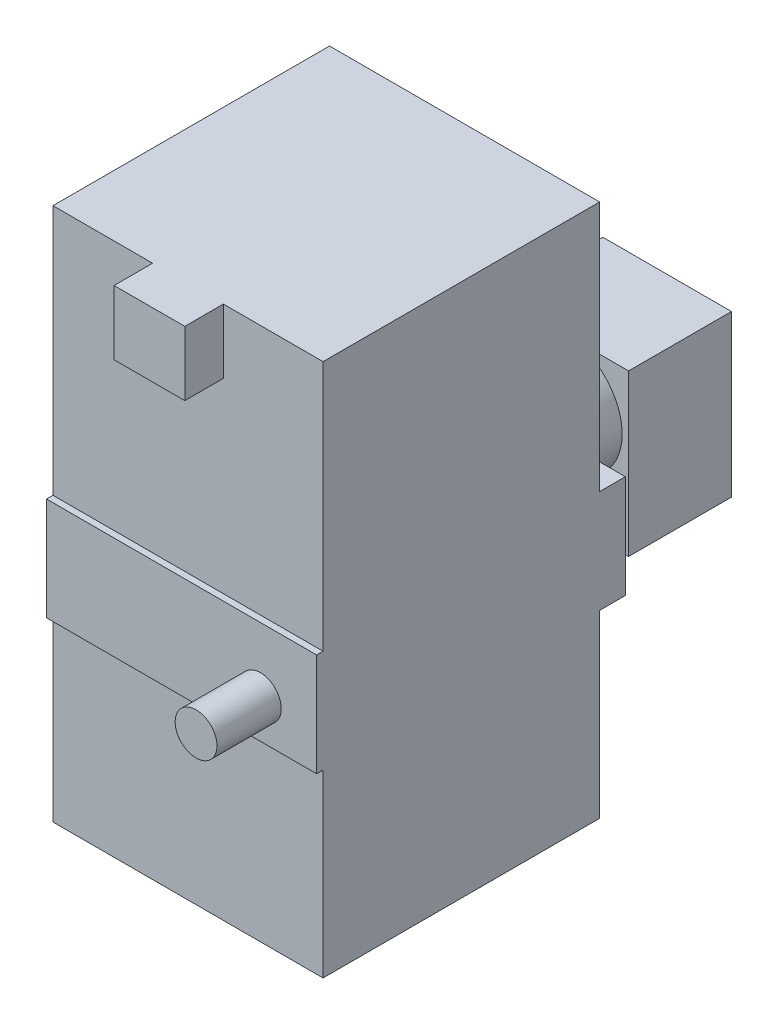
SolidWorks part; units mm, degrees
ref_plane "Alzado" through (0, 0, 0) normal (0, 0, 1) x (1, 0, 0)
ref_plane "Planta" through (0, 0, 0) normal (0, 1, 0) x (1, 0, 0)
ref_plane "Vista lateral" through (0, 0, 0) normal (1, 0, 0) x (0, 0, -1)
sketch "Croquis1" plane through (0, 0, 0) normal (1, 0, 0) x (0, 0, -1)
  line L0 (21.5, 2.5) -> (25.5, 2.5)
  line L1 (21.5, -41.5) -> (-21.5, -41.5)
  line L2 (21.5, -41.5) -> (21.5, -13.5)
  line L3 (21.5, 41.5) -> (-21.5, 41.5)
  line L4 (-21.5, -41.5) -> (-21.5, -13.5)
  line L5 (21.5, -41.5) -> (-21.5, 41.5) construction
  line L6 (21.5, 41.5) -> (-21.5, -41.5) construction
  line L7 (-22.5, -13.5) -> (-21.5, -13.5)
  line L8 (-22.5, -13.5) -> (-22.5, 2.5)
  line L9 (-22.5, 2.5) -> (-21.5, 2.5)
  line L10 (25.5, -13.5) -> (25.5, 2.5)
  line L11 (21.5, 2.5) -> (21.5, 41.5)
  line L12 (21.5, -13.5) -> (25.5, -13.5)
  line L13 (-21.5, 2.5) -> (-21.5, 41.5)
  point P0 (0, 0)
  dimension "D1" = 43
  dimension "D2" = 83
  dimension "D3" = 48
  dimension "D4" = 4
  dimension "D5" = 16
  dimension "D6" = 39
extrude "Saliente-Extruir1" add sketch "Croquis1" along normal blind 42
sketch "Croquis2" plane through (0, 0, 21.5) normal (0, 0, 1) x (1, 0, 0)
  line L0 (42, 41.5) -> (0, 41.5) construction
  line L1 (15.5, 41.5) -> (26.5, 41.5)
  line L2 (15.5, 41.5) -> (15.5, 31.5)
  line L3 (15.5, 31.5) -> (26.5, 31.5)
  line L4 (26.5, 41.5) -> (26.5, 31.5)
  line L5 (15.5, 41.5) -> (0, 41.5) construction
  line L6 (26.5, 41.5) -> (42, 41.5) construction
  dimension "D1" = 10
  dimension "D2" = 11
extrude "Saliente-Extruir2" add sketch "Croquis2" along normal blind 6
sketch "Croquis3" plane through (0, 0, 22.5) normal (0, 0, 1) x (1, 0, 0)
  line L0 (42, 2.5) -> (0, 2.5) construction
  line L1 (42, 2.5) -> (42, -13.5) construction
  circle A0 centre (33.25, -7.5) radius 3.25
  dimension "D1" = 6.5
  dimension "D2" = 10
  dimension "D3" = 8.75
extrude "Saliente-Extruir3" add sketch "Croquis3" along normal blind 10
sketch "Croquis4" plane through (0, 0, -25.5) normal (0, 0, -1) x (-1, 0, 0)
  line L1 (-42, 2.5) -> (0, 2.5) construction
  line L3 (0, -13.5) -> (0, 2.5) construction
  circle A0 centre (-16, -8.5) radius 9
  dimension "D2" = 18
  dimension "D3" = 16
  dimension "D1" = 11
extrude "Saliente-Extruir4" add sketch "Croquis4" along normal blind 16.5
sketch "Croquis5" plane through (0, 0, -42) normal (0, 0, -1) x (-1, 0, 0)
  line L0 (-16, 0.5) -> (-16, -17.5) construction
  line L1 (-26, 0.5) -> (-6, 0.5)
  line L2 (-26, 0.5) -> (-26, -24.5)
  line L3 (-26, -24.5) -> (-6, -24.5)
  line L4 (-6, 0.5) -> (-6, -24.5)
  arc A1 (-8.5167, -13.5) -> (-23.4833, -13.5) centre (-16, -8.5) ccw construction
  circle A2 centre (-16, -8.5) radius 9 construction
  dimension "D1" = 20
  dimension "D2" = 25
extrude "Saliente-Extruir5" add sketch "Croquis5" along normal blind 16
sketch "Croquis6" plane through (0, 0, -58) normal (0, 0, -1) x (-1, 0, 0)
  circle A0 centre (-16, -8.5) radius 3.5
  dimension "D1" = 7
extrude "Saliente-Extruir6" add sketch "Croquis6" along normal blind 1
fillet "Redondeo2" radius 4 1 edges at (12.5, -8.5, -59)
sketch "Croquis7" plane through (0, 0.5, 0) normal (0, 1, 0) x (1, 0, 0)
  line L0 (16, 42) -> (16, 58) construction
  line L1 (6, 58) -> (26, 58) construction
sketch "Croquis9" plane through (0, 0, -25.5) normal (0, 0, -1) x (-1, 0, 0)
  line L0 (0, -8.5) -> (-42, -8.5) construction
  line L1 (0, -13.5) -> (0, 2.5) construction
  line L2 (-42, -13.5) -> (-42, 2.5) construction
  line L3 (-42, 2.5) -> (0, 2.5) construction
  dimension "D1" = 11
sketch "Croquis10" plane through (42, 0, 0) normal (1, 0, 0) x (0, 0, -1)
  line L0 (25.5, -8.5) -> (-22.5, -8.5) construction
  line L1 (-22.5, 2.5) -> (-22.5, -13.5) construction
